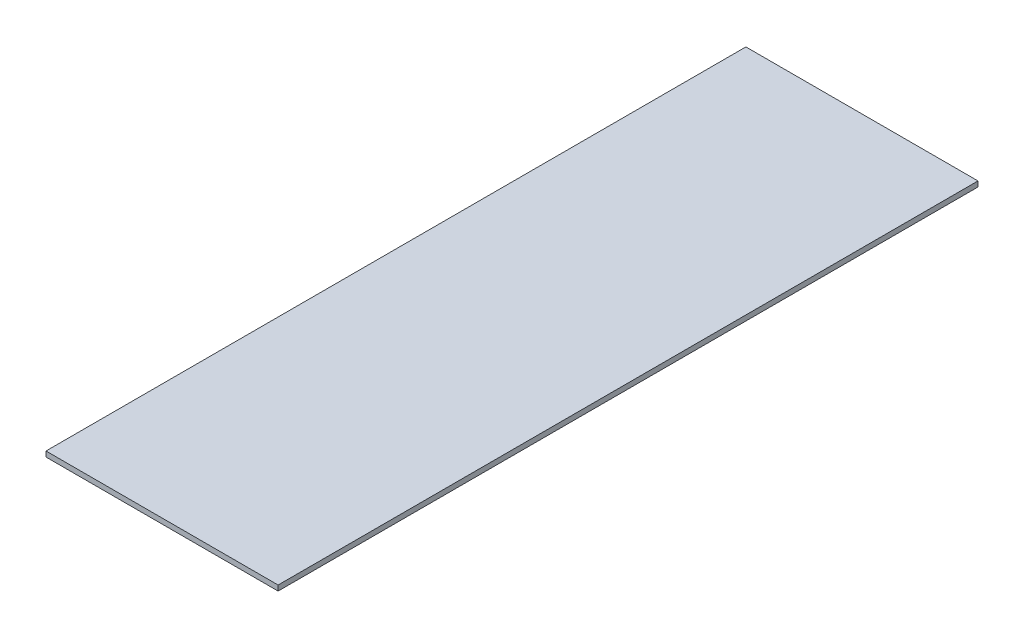
SolidWorks part; units mm, degrees
ref_plane "Front Plane" through (0, 0, 0) normal (0, 0, 1) x (1, 0, 0)
ref_plane "Top Plane" through (0, 0, 0) normal (0, 1, 0) x (1, 0, 0)
ref_plane "Right Plane" through (0, 0, 0) normal (1, 0, 0) x (0, 0, -1)
sketch "Sketch1" plane through (0, 0, 0) normal (0, 0, 1) x (1, 0, 0)
  line L1 (0, 0) -> (1676.4, 0)
  line L2 (0, 0) -> (0, 38.1)
  line L3 (0, 38.1) -> (1676.4, 38.1)
  line L4 (1676.4, 0) -> (1676.4, 38.1)
  dimension "D1" = 1676.4
  dimension "D2" = 38.1
extrude "Boss-Extrude1" add sketch "Sketch1" along normal blind 5054.6
